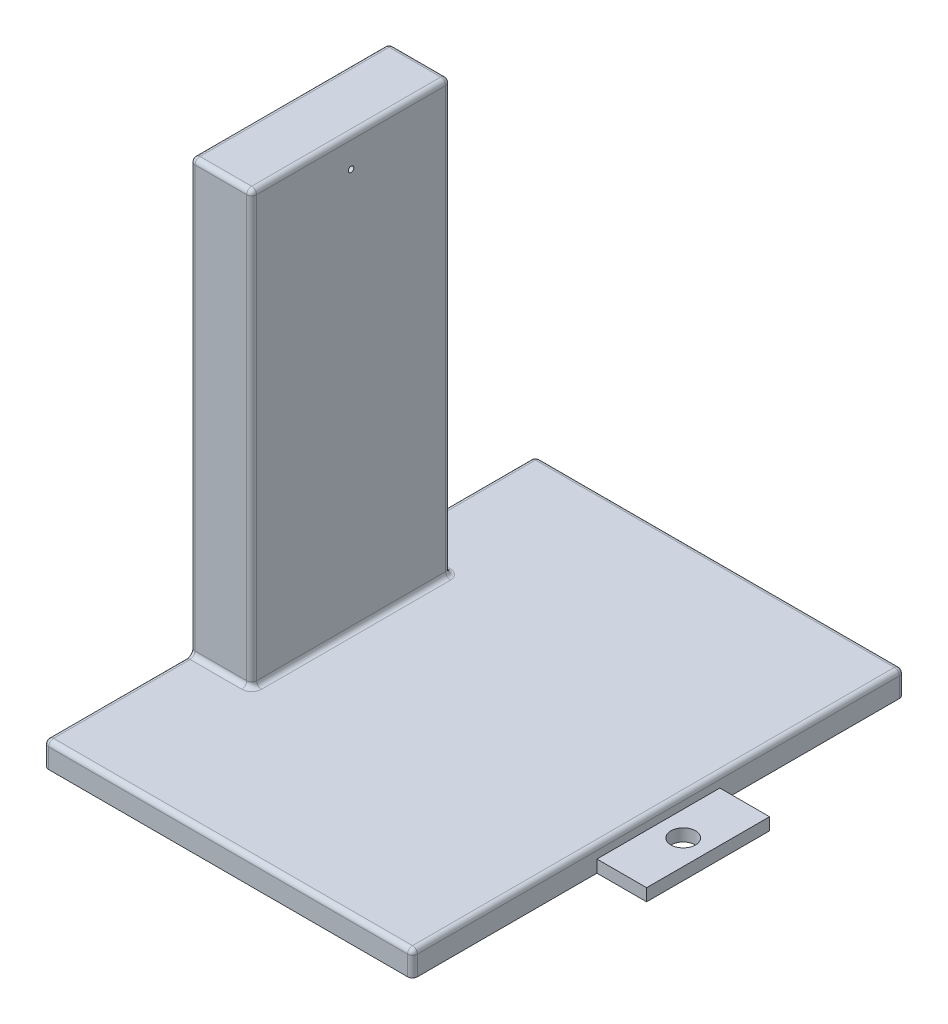
SolidWorks part; units mm, degrees
ref_plane "Plan de face" through (0, 0, 0) normal (0, 0, 1) x (1, 0, 0)
ref_plane "Plan de dessus" through (0, 0, 0) normal (0, 1, 0) x (1, 0, 0)
ref_plane "Plan de droite" through (0, 0, 0) normal (1, 0, 0) x (0, 0, -1)
sketch "Esquisse2" plane through (0, 0, 0) normal (0, 1, 0) x (1, 0, 0)
  line L0 (75, 100) -> (-75, 100)
  line L1 (75, -100) -> (75, 100)
  line L2 (-75, -100) -> (75, -100)
  line L3 (-75, 100) -> (-75, -100)
extrude "Boss.-Extru.2" add sketch "Esquisse2" along normal blind 10
sketch "Esquisse3" plane through (0, 0, 0) normal (0, 1, 0) x (1, 0, 0)
  line L0 (-75, 40.4491) -> (-75, -40.4491)
  line L1 (-75, -40.4491) -> (-50, -40.4491)
  line L2 (-50, -40.4491) -> (-50, 40.4491)
  line L3 (-50, 40.4491) -> (-75, 40.4491)
extrude "Boss.-Extru.3" add sketch "Esquisse3" along normal blind 165
sketch "Esquisse7" plane through (0, 0, 0) normal (1, 0, 0) x (0, 0, -1)
  line L0 (-100, 0) -> (100, 0) construction
  line L1 (-25, 5) -> (-25, 0)
  line L2 (25, 5) -> (-25, 5)
  line L3 (25, 0) -> (25, 5)
  line L4 (-25, 0) -> (25, 0)
  point P8 (0, 0)
extrude "Boss.-Extru.4" add sketch "Esquisse7" along normal blind 95.2
sketch "Esquisse8" plane through (0, 0, 0) normal (0, 1, 0) x (1, 0, 0)
  circle A0 centre (85.1, 0) radius 5
extrude "Enlèv. mat.-Extru.2" cut sketch "Esquisse8" against normal blind 95.2 and the other way blind 95.2
sketch "Esquisse9" plane through (0, 0, 0) normal (0, 1, 0) x (1, 0, 0)
  line L4 (-50, 40.4491) -> (-75, 40.4491)
  line L5 (-75, 40.4491) -> (-75, -40.4491)
  line L6 (-75, -40.4491) -> (-50, -40.4491)
  line L7 (-50, -40.4491) -> (-50, 40.4491)
  line L8 (-50, 40.4491) -> (-75, 40.4491)
  line L9 (-75, 40.4491) -> (-75, -40.4491)
  line L10 (-75, -40.4491) -> (-50, -40.4491)
  line L11 (-50, -40.4491) -> (-50, 40.4491)
  dimension "D1" = 0
extrude "Boss.-Extru.5" add sketch "Esquisse9" along normal blind 185.2
sketch "Esquisse10" plane through (0, 0, 0) normal (1, 0, 0) x (0, 0, -1)
  line L1 (0, 185.2) -> (0, 172.95) construction
  line L2 (-40.4491, 185.2) -> (40.4491, 185.2) construction
  circle A0 centre (0, 172.95) radius 1.125
  dimension "D2" = 2.25
  dimension "D1" = 12.25
extrude "Boss.-Extru.6" add sketch "Esquisse10" along normal blind 2 separate body
fillet "Congé2" radius 2 20 edges at (-75, 97.6, -40.4491) (-75, 185.2, 0) (-62.5, 185.2, -40.4491) (-75, 97.6, 40.4491) (-62.5, 185.2, 40.4491) (0, 10, -100) (75, 10, 0) (0, 10, 100) (-75, 10, 70.2246) (-62.5, 10, 40.4491) (-62.5, 10, -40.4491) (-75, 10, -70.2246) (-50, 97.6, 40.4491) (-50, 185.2, 0) (-50, 97.6, -40.4491) (-50, 10, 0) (75, 5, 100) (75, 5, -100) (-75, 5, -100) (-75, 5, 100)
sketch "Esquisse11" plane through (0, 0, 0) normal (1, 0, 0) x (0, 0, -1)
  circle A1 centre (0, 172.95) radius 1.125
  circle A2 centre (0, 172.95) radius 1.125
  dimension "D1" = 0
extrude "Enlèv. mat.-Extru.4" cut sketch "Esquisse11" against normal blind 150 and the other way blind 150
